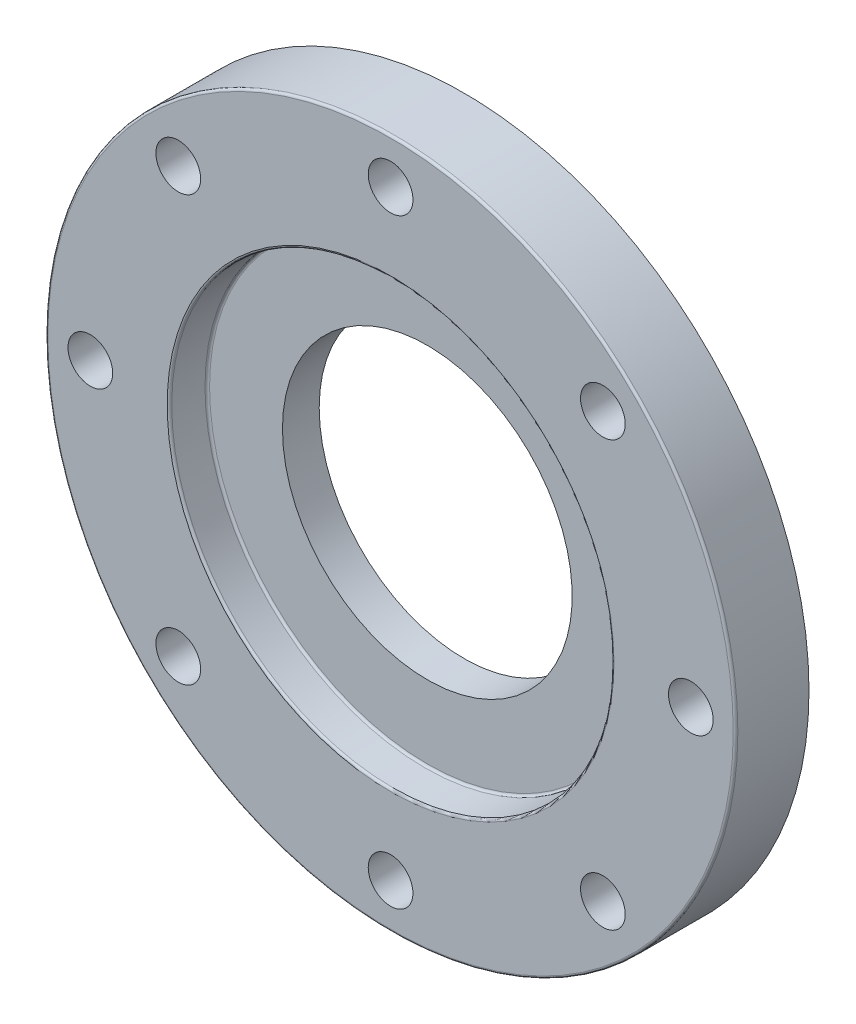
SolidWorks part; units mm, degrees
ref_plane "Front Plane" through (0, 0, 0) normal (0, 0, 1) x (1, 0, 0)
ref_plane "Top Plane" through (0, 0, 0) normal (0, 1, 0) x (1, 0, 0)
ref_plane "Right Plane" through (0, 0, 0) normal (1, 0, 0) x (0, 0, -1)
sketch "Sketch0" plane through (0, 0, 0) normal (1, 0, 0) x (0, 0, -1)
  line L0 (0, 0) -> (-36.5125, 0) construction
  point P3 (-36.5125, 0)
  point P4 (-5.5562, 0)
  dimension "Q" = 36.5125
  dimension "N" = 5.5562
sketch "Sketch1" plane through (0, 0, 0) normal (0, 0, 1) x (1, 0, 0)
  circle A0 centre (0, 0) radius 171.45
  circle A1 centre (0, 0) radius 109.9185 construction
  circle A2 centre (0, 0) radius 149.225 construction
  circle A3 centre (0, 149.225) radius 11.1125 construction
  circle A6 centre (0, 0) radius 109.347 construction
  point P9 (0, 109.9185)
  point P10 (0, 109.347)
  dimension "A" = 342.9
  dimension "B" = 298.45
  dimension "Bolt Hole Size" = 22.225
  dimension "Pipe OD A" = 219.837
  dimension "Pipe OD B" = 218.694
extrude "Extrude1" add sketch "Sketch1" along normal up to vertex (36.5125 mm away) up to point (0, 0, 36.5125)
sketch "Sketch2" plane through (0, 0, 36.5125) normal (0, 0, 1) x (1, 0, 0)
  circle A0 centre (0, 149.225) radius 11.1125 construction
  circle A1 centre (0, 149.225) radius 11.1125
extrude "Extrude2" cut sketch "Sketch2" against normal through all
ref_axis "Axis1" through (0, 0, -1.6272) along (0, 0, 1)
pattern_circular "CirPattern1" count 8 over 360 about axis through (0, 0, -1.6272) along (0, 0, 1) of "Extrude2"
sketch "Sketch3" plane through (0, 0, 0) normal (1, 0, 0) x (0, 0, -1)
  line L0 (-36.5125, 109.9185) -> (-18.2563, 109.347)
  line L1 (-18.2563, 109.347) -> (-18.2562, 0)
  line L2 (0, 0) -> (-36.5125, 0) construction
  line L3 (-18.2562, 0) -> (-36.5125, 0)
  line L4 (-36.5125, 0) -> (-36.5125, 109.9185)
  line L5 (0, 109.347) -> (-18.2563, 109.347) construction
  line L6 (-36.5125, 109.9185) -> (0, 109.9185) construction
revolve "Cut-Revolve1" cut sketch "Sketch3" angle 360 about L3
fillet "Fillet1" radius 1.1545 3 edges at (171.45, 0, 36.5125) (0, 109.347, 18.2563) (0, 109.9185, 36.5125) tangent propagation no
sketch "Sketch5" plane through (0, 0, 0) normal (0, 0, -1) x (-1, 0, 0)
  circle A0 centre (0, 0) radius 72
  dimension "D1" = 144
extrude "Cut-Extrude1" cut sketch "Sketch5" against normal blind 237.236 contours A0
